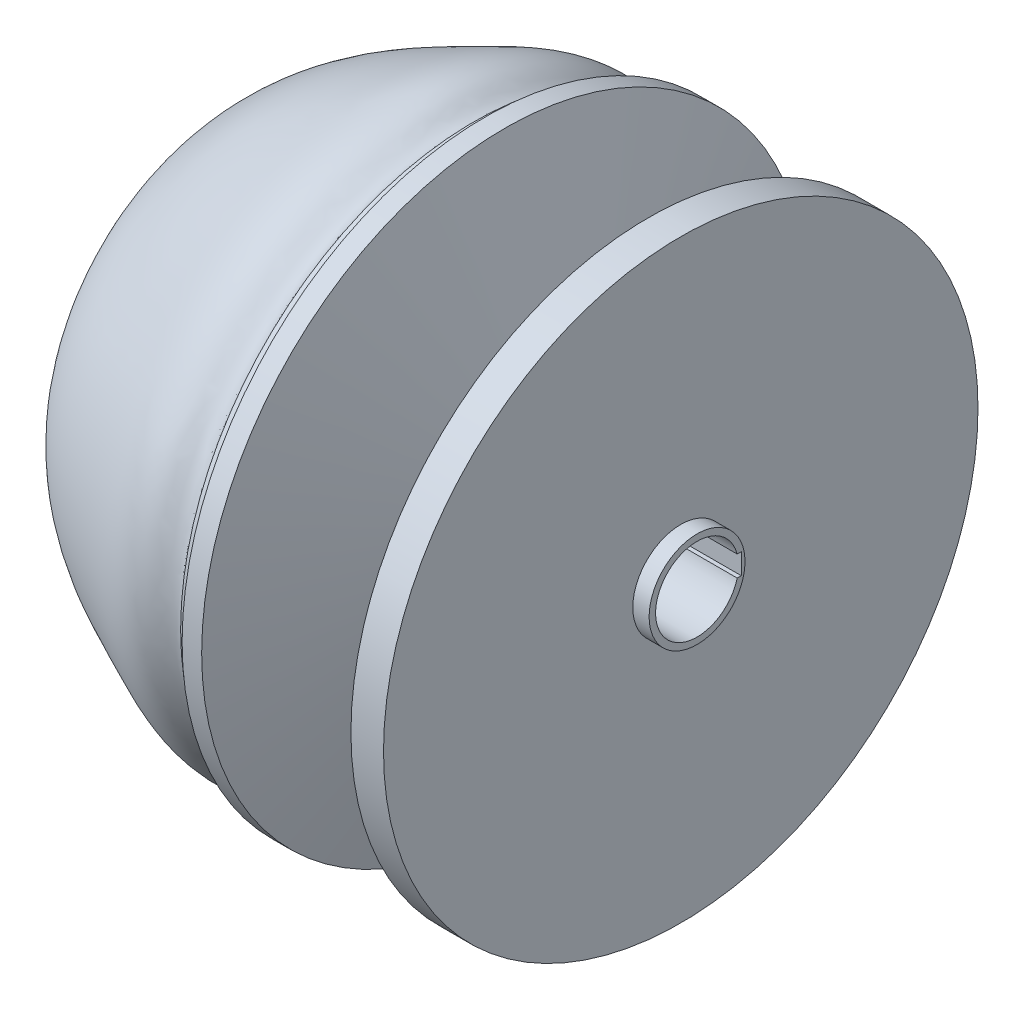
SolidWorks part; units mm, degrees
ref_plane "Front Plane" through (0, 0, 0) normal (0, 0, 1) x (1, 0, 0)
ref_plane "Top Plane" through (0, 0, 0) normal (0, 1, 0) x (1, 0, 0)
ref_plane "Right Plane" through (0, 0, 0) normal (1, 0, 0) x (0, 0, -1)
sketch "Sketch1" plane through (0, 0, 0) normal (0, 0, 1) x (1, 0, 0)
  line L0 (-81.8357, 0) -> (85.1506, 0) construction
  line L1 (-80.912, 0) -> (-80.912, 12.718)
  line L2 (-80.912, 12.718) -> (-70.912, 12.718)
  line L3 (-70.912, 12.718) -> (-70.912, 32.718)
  line L4 (10.8811, 90) -> (14.335, 90)
  line L5 (14.335, 90) -> (14.335, 93)
  line L6 (14.335, 93) -> (20.335, 93)
  line L7 (20.335, 93) -> (41.2272, 15)
  line L8 (41.2272, 15) -> (53.8702, 15)
  line L9 (53.8702, 15) -> (64.335, 91.2022)
  line L10 (64.335, 91.2022) -> (74.335, 91.2022)
  line L11 (74.335, 91.2022) -> (74.335, 14.7093)
  line L12 (74.335, 14.7093) -> (79.335, 14.7093)
  line L13 (79.335, 14.7093) -> (79.335, 0)
  line L14 (-80.912, 0) -> (79.335, 0)
  spline S0 degree 3 poles (-70.912, 32.718) (-72.1206, 49.6249) (-53.0866, 70.2231) (-24.9006, 82.1714) (-2.5694, 92.8185) (6.8991, 82.6166) (10.8811, 90) knots 0 0 0 0 0.424566 0.683651 0.890381 1 1 1 1
  dimension "D1" = 10
  dimension "D2" = 15
  dimension "D3" = 93
  dimension "D4" = 160.247
  dimension "D5" = 10
  dimension "D6" = 5
  dimension "D7" = 6
  dimension "D8" = 3
  dimension "D9" = 44
revolve "Revolve1" add sketch "Sketch1" angle 360 about L0
sketch "Sketch2" plane through (79.335, 0, 0) normal (1, 0, 0) x (0, 0, -1)
  circle A0 centre (0, 0) radius 12.718
  dimension "D1" = 25.436
extrude "Cut-Extrude1" cut sketch "Sketch2" against normal blind 82.74
sketch "Sketch3" plane through (-80.912, 0, 0) normal (-1, 0, 0) x (0, 0, 1)
  circle A0 centre (0, 0) radius 10
  dimension "D1" = 20
extrude "Cut-Extrude2" cut sketch "Sketch3" against normal blind 79.507
chamfer "Chamfer1" distance 3 angle 30 1 edges at (-3.405, 0, -10) first distance on face at (-3.405, 0, -10)
sketch "Sketch4" plane through (79.335, 0, 0) normal (1, 0, 0) x (0, 0, -1)
  line L1 (11.8725, 3.1875) -> (13.5635, 3.1875)
  line L2 (11.8725, 3.1875) -> (11.8725, -3.1875)
  line L3 (11.8725, -3.1875) -> (13.5635, -3.1875)
  line L4 (13.5635, 3.1875) -> (13.5635, -3.1875)
  line L5 (11.8725, 3.1875) -> (13.5635, -3.1875) construction
  line L6 (11.8725, -3.1875) -> (13.5635, 3.1875) construction
  circle A0 centre (0, 0) radius 12.718 construction
  circle A1 centre (0, 0) radius 12.718 construction
  point P0 (12.718, 0)
  dimension "D1" = 6.375
  dimension "D2" = 0.8455
extrude "Cut-Extrude3" cut sketch "Sketch4" against normal blind 56
